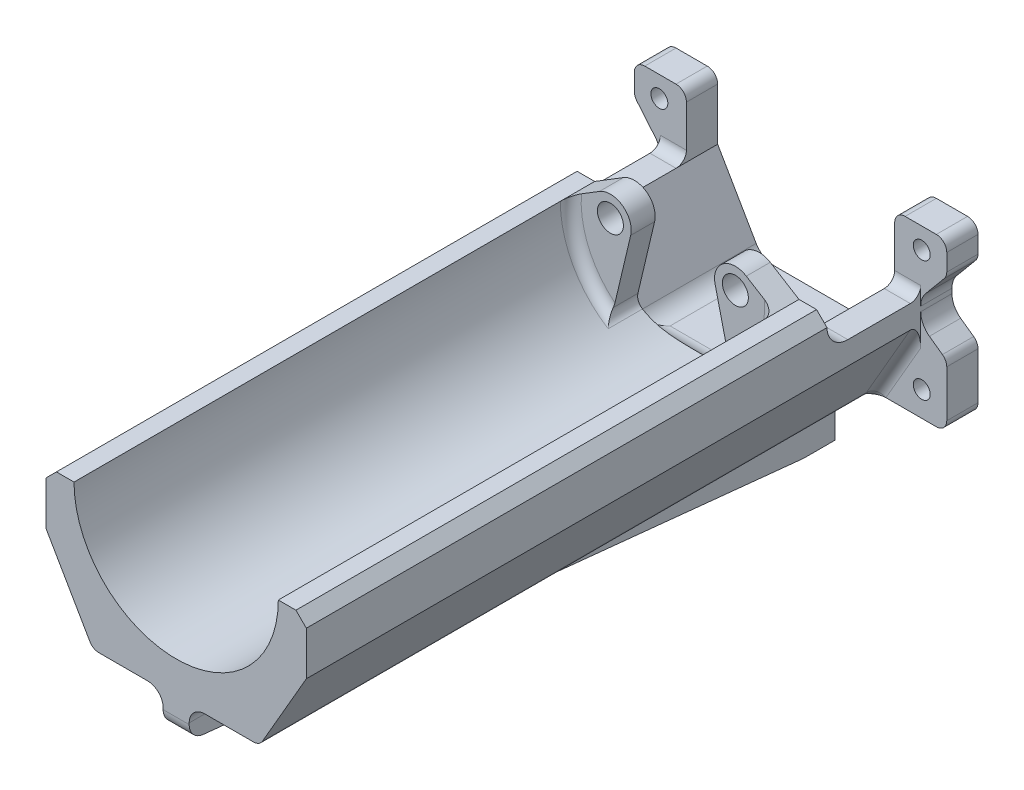
SolidWorks part; units mm, degrees
ref_plane "Front Plane" through (0, 0, 0) normal (0, 0, 1) x (1, 0, 0)
ref_plane "Top Plane" through (0, 0, 0) normal (0, 1, 0) x (1, 0, 0)
ref_plane "Right Plane" through (0, 0, 0) normal (1, 0, 0) x (0, 0, -1)
sketch "Sketch1" plane through (0, 0, 0) normal (0, 0, 1) x (1, 0, 0)
  line L0 (-12.4587, 0) -> (-15.875, 0)
  line L1 (-15.875, 0) -> (-15.875, -16.51)
  line L2 (-15.875, -16.51) -> (15.875, -16.51)
  line L3 (15.875, -16.51) -> (15.875, 0)
  line L4 (15.875, 0) -> (12.4587, 0)
  arc A0 (-12.4587, 0) -> (12.4587, 0) centre (0, 0) ccw
  dimension "D1" = 24.9174
  dimension "D2" = 31.75
  dimension "D3" = 16.51
extrude "Boss-Extrude1" add sketch "Sketch1" along normal blind 63.5
sketch "Sketch2" plane through (0, 0, 0) normal (0, 0, -1) x (-1, 0, 0)
  line L0 (0, 0) -> (0, 50000) construction
  line L1 (-8.9533, 2.1619) -> (-12.4587, 0)
  line L2 (-7.62, 0) -> (0, 0) construction
  line L3 (5.1485, -0.5859) -> (7.3878, -10.032)
  line L5 (-12.4587, 0) -> (-15.875, 0)
  line L6 (-15.875, 0) -> (-15.875, -16.51)
  line L7 (-15.875, -16.51) -> (15.875, -16.51)
  line L8 (15.875, -16.51) -> (15.875, 0)
  line L9 (15.875, 0) -> (12.4587, 0)
  line L10 (-12.4587, 0) -> (-15.875, 0)
  line L11 (-15.875, 0) -> (-15.875, -16.51)
  line L12 (-15.875, -16.51) -> (15.875, -16.51)
  line L13 (15.875, -16.51) -> (15.875, 0)
  line L14 (15.875, 0) -> (12.4587, 0)
  line L16 (-5.1485, -0.5859) -> (-7.3878, -10.032)
  line L17 (8.9533, 2.1619) -> (12.4587, 0)
  circle A0 centre (-7.62, 0) radius 1.5875
  arc A1 (-12.4587, 0) -> (12.4587, 0) centre (0, 0) ccw
  arc A4 (-5.1485, -0.5859) -> (-8.9533, 2.1619) centre (-7.62, 0) ccw
  arc A6 (-12.4587, 0) -> (12.4587, 0) centre (0, 0) ccw construction
  arc A7 (-7.3878, -10.032) -> (7.3878, -10.032) centre (0, 0) ccw
  arc A8 (5.1485, -0.5859) -> (8.9533, 2.1619) centre (7.62, 0) cw
  circle A9 centre (7.62, 0) radius 1.5875
  dimension "D2" = 3.175
  dimension "D3" = 7.62
  dimension "D4" = 5.08
  dimension "D5" = 45
  dimension "D1" = 0
extrude "Boss-Extrude2" add sketch "Sketch2" against normal blind 2.921
fillet "Fillet1" radius 1.27 4 edges at (11.1189, -5.6204, 2.921) (7.3878, -10.032, 1.4605) (-7.3878, -10.032, 1.4605) (-11.1189, -5.6204, 2.921)
chamfer "Chamfer1" distance 1.27 angle 45 2 edges at (15.875, 0, 31.75) (-15.875, 0, 31.75)
chamfer "Chamfer2" distance 5.715 angle 60 2 edges at (15.875, -16.51, 31.75) (-15.875, -16.51, 31.75)
sketch "Sketch3" plane through (0, 0, 0) normal (0, 0, -1) x (-1, 0, 0)
  line L1 (-15.875, -6.6113) -> (-15.875, -1.27) construction
  line L2 (-7.2741, -13.208) -> (7.2741, -13.208)
  line L4 (15.875, -1.27) -> (15.875, -6.6113) construction
  line L5 (-15.875, -3.81) -> (-15.875, -6.6113)
  line L6 (15.875, -3.81) -> (15.875, -6.6113)
  line L7 (-7.2741, -13.208) -> (-12.7, -3.81)
  line L8 (-12.7, -3.81) -> (-15.875, -3.81)
  line L9 (7.2741, -13.208) -> (12.7, -3.81)
  line L10 (12.7, -3.81) -> (15.875, -3.81)
  line L13 (-15.875, -1.27) -> (-15.875, -6.6113)
  line L14 (-15.875, -6.6113) -> (-10.16, -16.51)
  line L15 (-10.16, -16.51) -> (10.16, -16.51)
  line L16 (10.16, -16.51) -> (15.875, -6.6113)
  line L17 (15.875, -6.6113) -> (15.875, -1.27)
  line L18 (15.875, -1.27) -> (14.605, 0)
  line L19 (14.605, 0) -> (12.4587, 0)
  line L20 (12.4587, 0) -> (8.9533, 2.1619)
  line L21 (5.1485, -0.5859) -> (7.1863, -9.1822)
  line L22 (-7.1863, -9.1822) -> (-5.1485, -0.5859)
  line L23 (-8.9533, 2.1619) -> (-12.4587, 0)
  line L24 (-12.4587, 0) -> (-14.605, 0)
  line L25 (-14.605, 0) -> (-15.875, -1.27)
  line L27 (-15.875, -6.6113) -> (-10.16, -16.51)
  line L28 (-10.16, -16.51) -> (10.16, -16.51)
  line L29 (10.16, -16.51) -> (15.875, -6.6113)
  arc A5 (8.9533, 2.1619) -> (5.1485, -0.5859) centre (7.62, 0) ccw
  arc A6 (6.626, -10.5506) -> (7.1863, -9.1822) centre (5.9506, -9.4751) ccw
  arc A7 (-6.626, -10.5506) -> (6.626, -10.5506) centre (0, 0) ccw
  arc A8 (-7.1863, -9.1822) -> (-6.626, -10.5506) centre (-5.9506, -9.4751) ccw
  arc A9 (-5.1485, -0.5859) -> (-8.9533, 2.1619) centre (-7.62, 0) ccw
  dimension "D2" = 3.302
  dimension "D3" = 3.175
  dimension "D4" = 3.175
  dimension "D5" = 12.7
  dimension "D6" = 12.7
  dimension "D1" = 0
extrude "Boss-Extrude3" add sketch "Sketch3" along normal blind 11.43
sketch "Sketch4" plane through (0, 0, -11.43) normal (0, 0, -1) x (-1, 0, 0)
  line L0 (0, 0) -> (0, 50000) construction
  line L1 (0, 0) -> (50000, 0) construction
  line L7 (0, 0) -> (0, 50000) construction
  line L8 (19.05, -16.51) -> (-19.05, -16.51)
  line L9 (-10.16, -16.51) -> (10.16, -16.51) construction
  line L10 (-19.05, -16.51) -> (-19.05, -8.89)
  line L11 (-19.05, -8.89) -> (-15.875, -6.6113)
  line L13 (-12.7, -3.81) -> (-12.7, 3.81)
  line L14 (-12.7, 3.81) -> (-19.05, 3.81)
  line L15 (-19.05, 3.81) -> (-19.05, 0)
  line L16 (-19.05, 0) -> (-15.875, -3.81)
  line L17 (-15.875, -3.81) -> (-15.875, -6.6113) construction
  line L18 (-12.7, -3.81) -> (-15.875, -3.81) construction
  line L19 (-15.875, -3.81) -> (-15.875, -6.6113)
  line L20 (-12.7, -3.81) -> (-7.2741, -13.208)
  line L21 (-7.2741, -13.208) -> (7.2741, -13.208)
  line L22 (7.2741, -13.208) -> (-7.2741, -13.208) construction
  line L23 (12.7, -3.81) -> (7.2741, -13.208)
  line L24 (15.875, -3.81) -> (15.875, -6.6113)
  line L25 (19.05, 0) -> (15.875, -3.81)
  line L26 (19.05, 3.81) -> (19.05, 0)
  line L27 (12.7, 3.81) -> (19.05, 3.81)
  line L28 (12.7, -3.81) -> (12.7, 3.81)
  line L29 (19.05, -8.89) -> (15.875, -6.6113)
  line L30 (19.05, -16.51) -> (19.05, -8.89)
  arc A0 (-6.626, -10.5506) -> (6.626, -10.5506) centre (0, 0) ccw construction
  point P33 (0, -13.208)
  point P41 (0, -16.51)
  dimension "D1" = 38.1
  dimension "D2" = 38.1
  dimension "D3" = 20.32
  dimension "D4" = 16.51
  dimension "D5" = 7.62
extrude "Boss-Extrude4" add sketch "Sketch4" along normal blind 3.81
sketch "Sketch5" plane through (0, 0, -15.24) normal (0, 0, -1) x (-1, 0, 0)
  line L0 (0, 0) -> (0, 50000) construction
  line L1 (-12.7, 3.81) -> (-19.05, 3.81) construction
  line L2 (-19.05, 3.81) -> (-19.05, 0) construction
  line L3 (-19.05, -8.89) -> (-19.05, -16.51) construction
  line L4 (-19.05, -16.51) -> (19.05, -16.51) construction
  circle A0 centre (-16.002, 1.27) radius 1.035
  circle A1 centre (-16.002, -13.462) radius 1.035
  circle A2 centre (16.002, -13.462) radius 1.035
  circle A3 centre (16.002, 1.27) radius 1.035
  dimension "D3" = 2.0701
  dimension "D4" = 2.0701
  dimension "D1" = 2.54
  dimension "D2" = 3.048
  dimension "D5" = 3.048
  dimension "D6" = 3.048
extrude "Cut-Extrude1" cut sketch "Sketch5" against normal through all
fillet "Fillet2" radius 2.54 5 edges at (-14.2875, -3.81, 0) (14.2875, -3.81, 0) (-7.2741, -13.208, -7.62) (7.2741, -13.208, -7.62) (0, -13.208, 0)
fillet "Fillet3" radius 2.54 4 edges at (-15.875, -6.6113, -13.335) (-15.875, -3.81, -13.335) (15.875, -6.6113, -13.335) (15.875, -3.81, -13.335)
fillet "Fillet4" radius 1.27 12 edges at (10.16, -16.51, 26.035) (-10.16, -16.51, 26.035) (-19.05, -16.51, -13.335) (19.05, -16.51, -13.335) (-19.05, -8.89, -13.335) (19.05, -8.89, -13.335) (-12.7, 3.81, -13.335) (12.7, 3.81, -13.335) (-19.05, 0, -13.335) (-19.05, 3.81, -13.335) (19.05, 0, -13.335) (19.05, 3.81, -13.335)
fillet "Fillet5" radius 1.27 6 edges at (-10.0618, -16.3399, -11.43) (10.0618, -16.3399, -11.43) (-13.2008, -11.2432, -11.43) (13.2008, -11.2432, -11.43) (-14.2875, -3.81, -11.43) (14.2875, -3.81, -11.43)
ref_plane "midplane" through (0, 0, 0) normal (-1, 0, 0) x (0, 0, 1)
sketch "Sketch6" plane through (0, 0, 0) normal (-1, 0, 0) x (0, 0, 1)
  line L0 (63.5, -16.51) -> (-10.16, -16.51) construction
  line L1 (63.5, -16.51) -> (-10.16, -16.51)
  line L2 (-11.43, -16.51) -> (-10.16, -16.51) construction
  line L3 (-11.43, -16.51) -> (-15.24, -16.51) construction
  line L4 (-11.43, -16.51) -> (-10.16, -16.51)
  line L5 (-11.43, -16.51) -> (-15.24, -16.51)
  line L6 (63.5, -16.51) -> (63.5, -20.32)
  line L8 (-15.24, -27.94) -> (-15.24, -16.51)
  line L9 (-15.24, -27.94) -> (-11.43, -27.94)
  line L10 (-11.43, -27.94) -> (63.5, -20.32)
  dimension "D1" = 3.81
  dimension "D2" = 11.43
  dimension "D3" = 3.81
extrude "Boss-Extrude5" add sketch "Sketch6" along normal mid plane 3.175
fillet "Fillet6" radius 1.905 4 edges at (0, -20.32, 63.5) (1.5875, -16.51, 24.13) (0, -27.94, -11.43) (-1.5875, -16.51, 24.13)
equation "\"D4@Sketch5\"=\"D3@Sketch5\""
